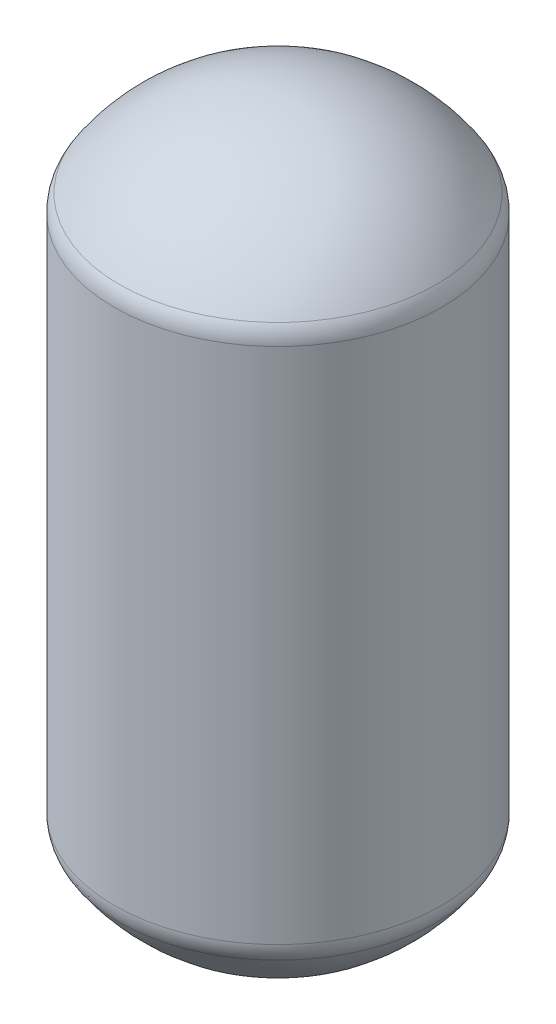
SolidWorks part; units mm, degrees
material "Custom Plastic"
ref_plane "Front Plane" through (0, 0, 0) normal (0, 0, 1) x (1, 0, 0)
ref_plane "Top Plane" through (0, 0, 0) normal (0, 1, 0) x (1, 0, 0)
ref_plane "Right Plane" through (0, 0, 0) normal (1, 0, 0) x (0, 0, -1)
sketch "Sketch1" plane through (0, 0, 0) normal (0, 0, 1) x (1, 0, 0)
  line L0 (0, 0) -> (0, 1200) construction
  line L1 (-133.985, 76.2) -> (133.985, 76.2) construction
  line L2 (-133.985, 0) -> (133.985, 0) construction
  line L3 (-133.985, 0) -> (-133.985, 1200) construction
  line L4 (-133.985, 1200) -> (133.985, 1200) construction
  line L5 (133.985, 0) -> (133.985, 1200) construction
  line L6 (-133.985, 0) -> (133.985, 1200) construction
  line L7 (-133.985, 1200) -> (133.985, 0) construction
  line L8 (-133.985, 685.1) -> (133.985, 685.1) construction
  line L9 (-133.985, 1123.8) -> (133.985, 1123.8) construction
  line L10 (-133.985, 608.9) -> (133.985, 608.9) construction
  line L11 (-133.985, 532.7) -> (133.985, 532.7) construction
  line L12 (-133.985, 608.9) -> (0, 608.9) construction
  line L13 (0, 608.9) -> (133.985, 608.9) construction
  line L14 (-133.985, 1123.8) -> (-133.985, 685.1)
  line L15 (133.985, 1123.8) -> (133.985, 685.1) construction
  line L16 (-133.985, 532.7) -> (-133.985, 76.2)
  line L17 (133.985, 532.7) -> (133.985, 76.2) construction
  line L18 (-130.81, 531.8223) -> (-130.81, 77.0777)
  line L19 (130.81, 531.8223) -> (130.81, 77.0777) construction
  line L20 (-130.81, 1122.9223) -> (-130.81, 685.9777)
  line L21 (130.81, 1122.9223) -> (130.81, 685.9777) construction
  line L22 (0, 3.175) -> (0, 0)
  line L23 (0, 605.725) -> (0, 608.9)
  line L24 (0, 612.075) -> (0, 608.9)
  line L25 (0, 1200) -> (0, 1196.825)
  arc A0 (0, 0) -> (-133.985, 76.2) centre (0, 155.8951) cw
  arc A1 (0, 0) -> (133.985, 76.2) centre (0, 155.8951) ccw construction
  arc A2 (0, 1200) -> (133.985, 1123.8) centre (0, 1044.1049) cw construction
  arc A3 (0, 1200) -> (-133.985, 1123.8) centre (0, 1044.1049) ccw
  arc A4 (0, 608.9) -> (-133.985, 532.7) centre (0, 453.0049) ccw
  arc A5 (0, 608.9) -> (133.985, 532.7) centre (0, 453.0049) cw construction
  arc A6 (0, 608.9) -> (-133.985, 685.1) centre (0, 764.7951) cw
  arc A7 (0, 608.9) -> (133.985, 685.1) centre (0, 764.7951) ccw construction
  arc A8 (0, 605.725) -> (-130.81, 531.8223) centre (0, 453.0049) ccw
  arc A9 (0, 3.175) -> (-130.81, 77.0777) centre (0, 155.8951) cw
  arc A10 (0, 3.175) -> (130.81, 77.0777) centre (0, 155.8951) ccw construction
  arc A11 (0, 605.725) -> (130.81, 531.8223) centre (0, 453.0049) cw construction
  arc A12 (0, 612.075) -> (-130.81, 685.9777) centre (0, 764.7951) cw
  arc A13 (0, 1196.825) -> (-130.81, 1122.9223) centre (0, 1044.1049) ccw
  arc A14 (0, 1196.825) -> (130.81, 1122.9223) centre (0, 1044.1049) cw construction
  arc A15 (0, 612.075) -> (130.81, 685.9777) centre (0, 764.7951) ccw construction
  point P3 (0, 600)
  dimension "D3" = 76.2
  dimension "D1" = 1200
  dimension "D2" = 267.97
  dimension "D4" = 76.2
  dimension "D5" = 76.2
  dimension "D6" = 1200
  dimension "D7" = 591.1
  dimension "D8" = 76.2
  dimension "D9" = 3.175
  dimension "D10" = 3.175
revolve "Revolve2" add sketch "Sketch1" angle 360 about L0 region at (-76.7692, 1179.0907, 0)
fillet "Fillet1" radius 25.4 4 edges at (0, 685.9777, -130.81) (0, 685.1, -133.985) (0, 1122.9223, -130.81) (0, 1123.8, -133.985)
